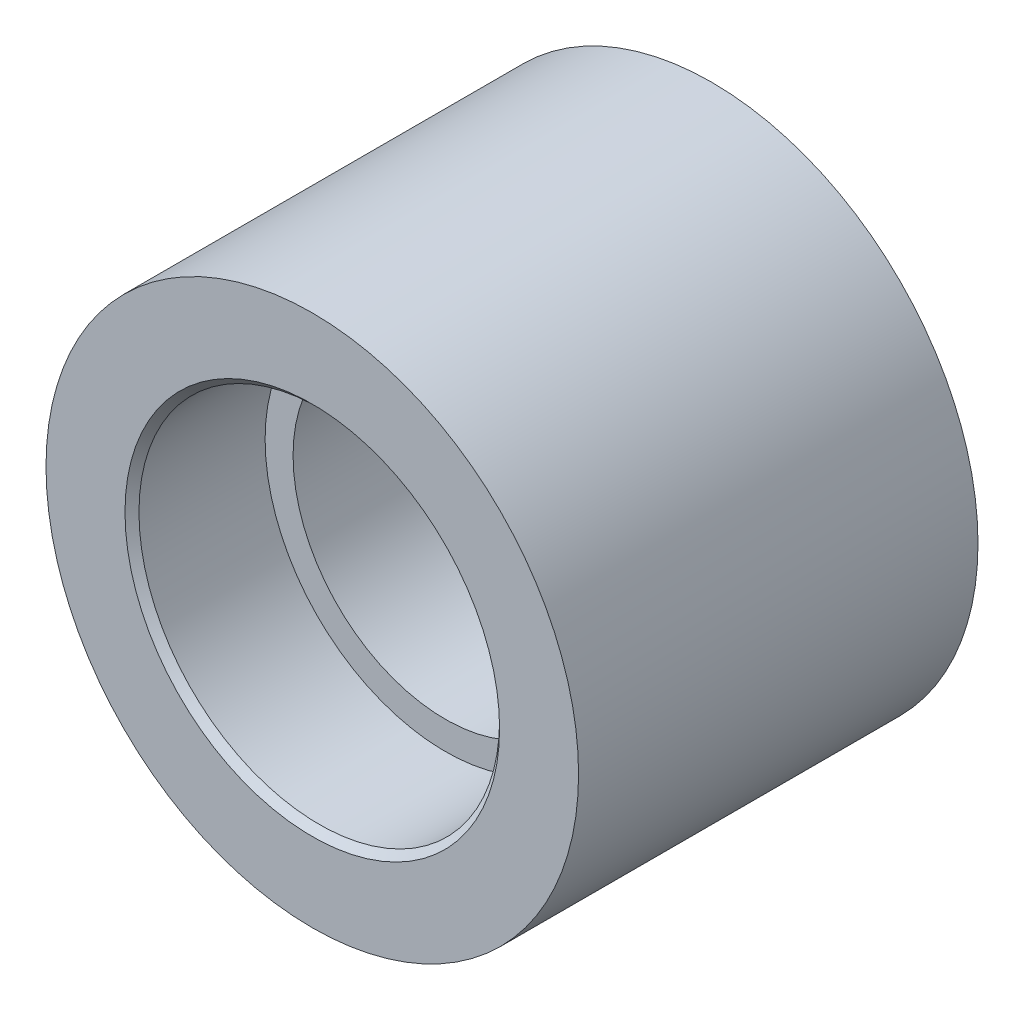
SolidWorks part; units mm, degrees
ref_plane "Front Plane" through (0, 0, 0) normal (0, 0, 1) x (1, 0, 0)
ref_plane "Top Plane" through (0, 0, 0) normal (0, 1, 0) x (1, 0, 0)
ref_plane "Right Plane" through (0, 0, 0) normal (1, 0, 0) x (0, 0, -1)
sketch "Sketch1" plane through (0, 0, 0) normal (0, 0, 1) x (1, 0, 0)
  circle A0 centre (0, 0) radius 6.45
  circle A1 centre (0, 0) radius 9.525
  dimension "D1" = 12.9
  dimension "D2" = 19.05
extrude "Boss-Extrude1" add sketch "Sketch1" along normal blind 14.2875
ref_plane "Plane1" through (0, 0, 7.1438) normal (0, 0, 1) x (1, 0, 0)
sketch "Sketch2" plane through (0, 0, 7.1438) normal (0, 0, 1) x (1, 0, 0)
  circle A0 centre (0, 0) radius 6.45 construction
  circle A1 centre (0, 0) radius 6.45
  circle A2 centre (0, 0) radius 5.45
  dimension "D1" = 1
extrude "Boss-Extrude2" add sketch "Sketch2" along normal mid plane 4.7625
chamfer "Chamfer1" distance 0.25 angle 45 2 edges at (6.45, 0, 0) (6.45, 0, 14.2875)
equation "\"D1@Boss-Extrude1\"=3in*3/16"
